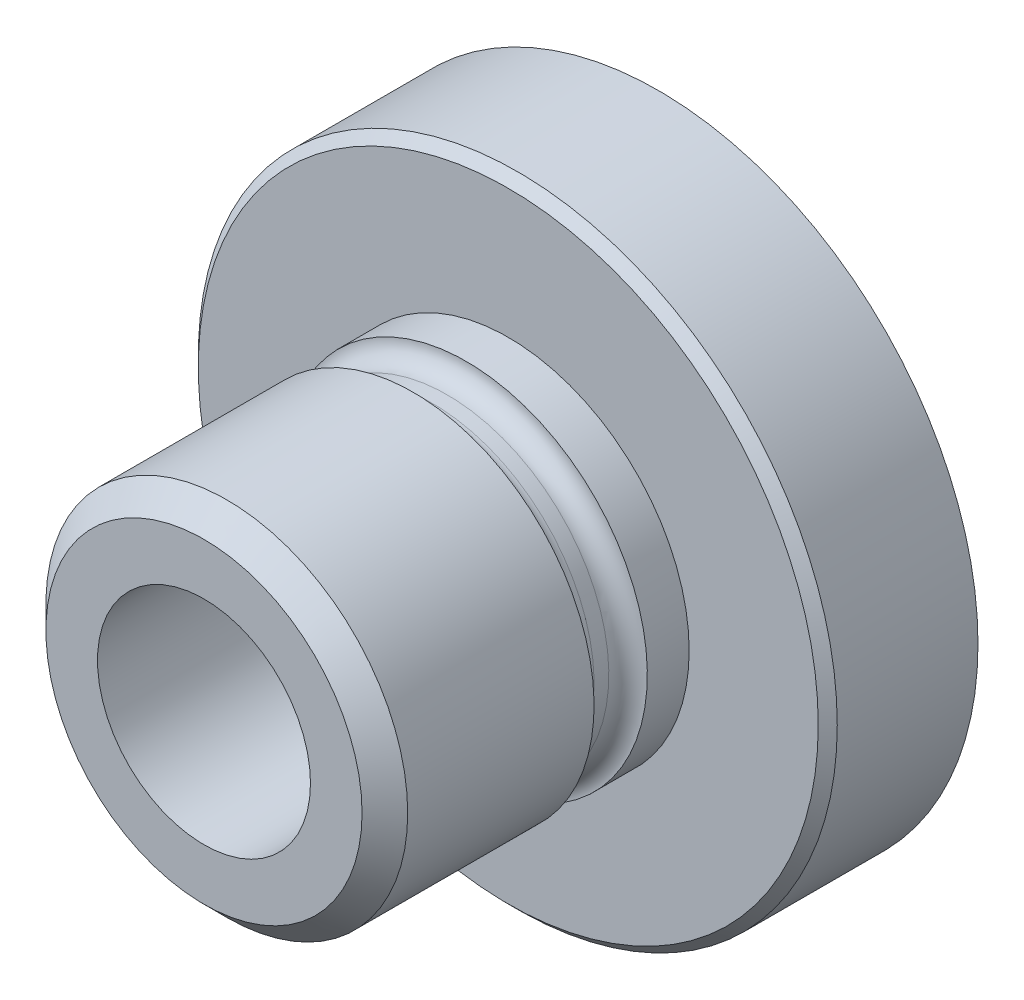
SolidWorks part; units mm, degrees
note: '?' marks a value the reader was unsure of.
ref_plane "Front" through (0, 0, 0) normal (0, 0, 1) x (1, 0, 0)
ref_plane "Top" through (0, 0, 0) normal (0, 1, 0) x (1, 0, 0)
ref_plane "Right" through (0, 0, 0) normal (1, 0, 0) x (0, 0, -1)
sketch "Sketch1" plane through (0, 0, 0) normal (0, 0, 1) x (1, 0, 0)
  circle A0 centre (0, 0) radius 16.8
  dimension "D1" = 33.6
extrude "Extrude1" add sketch "Sketch1" along normal blind 7.9
sketch "Sketch2" plane through (0, 0, 7.9) normal (0, 0, 1) x (1, 0, 0)
  circle A0 centre (0, 0) radius 9.5123
  dimension "D1" = 19.0246
extrude "THREAD" add sketch "Sketch2" along normal blind 16
sketch "Sketch3" plane through (0, 0, 0) normal (1, 0, 0) x (0, 0, -1)
  line L0 (-7.9, 9.5123) -> (-23.9, 9.5123) construction
  line L2 (-11.8877, 8.5) -> (-11.1123, 8.5)
  line L4 (-10.1, 9.5123) -> (-12.9, 9.5123)
  line L5 (-23.9, 9.5123) -> (-23.9, -9.5123) construction
  line L6 (-23.9, 0) -> (0, 0) construction
  arc A0 (-11.8877, 8.5) -> (-12.9, 9.5123) centre (-11.8877, 9.5123) cw
  arc A1 (-10.1, 9.5123) -> (-11.1123, 8.5) centre (-11.1123, 9.5123) cw
  dimension "D1" = 13.8
  dimension "D2" = 2.8
  dimension "D3" = 17
revolve "THREAD END" cut sketch "Sketch3" angle 360 about L6
chamfer "Chamfer1" distance 1.2 angle 45 1 edges at (9.5123, 0, 23.9)
chamfer "Chamfer2" distance 0.5 angle 45 1 edges at (16.8, 0, 7.9)
ref_plane "Plane1" through (0, 16.8, 0) normal (0, 1, 0) x (-1, 0, 0)
hole_wizard "1/8 NPT Tapped Hole1" [suppressed] positions "Sketch5" profile "Sketch4" size "1/8" standard "Ansi Inch"
sketch "Sketch5" plane through (0, 11, 0) normal (0, 1, 0) x (-1, 0, 0)
  line L0 (-11, 0) -> (11, 0) construction
  point P1 (0, 6.3)
  dimension "D1" = 9.5
sketch "Sketch4" plane through (0, 11, 6.3) normal (1, 0, 0) x (0, 0, 1)
  line L0 (0, 0) -> (0, 14.2325)
  line L1 (4.2164, 11.699) -> (0, 14.2325)
  line L2 (-4.2164, 11.699) -> (0, 14.2325) construction
  line L3 (4.2164, 11.699) -> (4.2164, 7)
  line L4 (4.2164, 7) -> (4.9362, 7)
  line L5 (4.9362, 7) -> (5.1458, 0)
  line L6 (-4.9362, 7) -> (-5.1458, 0) construction
  line L7 (5.1458, 0) -> (0, 0)
  line L8 (0, -6.35) -> (0, 107.95) construction
  line L11 (-4.2164, 7) -> (-4.9362, 7) construction
  dimension "Tap Drill Dia." = 8.4328
  dimension "Tap Drill Depth" = 11.699
  dimension "Thread Dia." = 10.2915
  dimension "Thread Angle" = 3.43
  dimension "Thread Depth" = 7
  dimension "Drill Angle" = 118
ref_axis "Axis1" [suppressed] through (0, 11, 6.3) along (0, -1, 0)?
sketch "Sketch6" [suppressed] plane through (0, 0, 0) normal (1, 0, 0) x (0, 0, -1)
  line L0 (-1.2, 11) -> (-1.2, 10)
  line L1 (-1.2, 10) -> (-0.2, 11)
  line L2 (0, 11) -> (-1.1542, 11) construction
  line L3 (-0.2, 11) -> (-1.2, 11)
  line L4 (0, -11) -> (0, 11) construction
  dimension "D1" = 45
  dimension "D2" = 1.1
  dimension "D3" = 4.4
revolve "Cut-Revolve1" [suppressed] cut sketch "Sketch6" angle 360 about axis through (0, 11, 6.3) along (0, -1, 0)
hole_wizard "1/4 NPT Tapped Hole1" [suppressed] positions "Sketch8" profile "Sketch7" size "1/4" standard "Ansi Inch"
sketch "Sketch8" plane through (0, 10.2, 0) normal (0, 1, 0) x (-1, 0, 0)
  line L0 (0, 0) -> (0, 4.8) construction
  line L1 (-10.2, 0) -> (10.2, 0) construction
  line L2 (-10.2, 4.8) -> (10.2, 4.8) construction
  point P1 (0, 18.2)
  dimension "D1" = 18.2
sketch "Sketch7" plane through (0, 10.2, 18.2) normal (1, 0, 0) x (0, 0, 1)
  line L0 (0, 0) -> (0, 14.3423)
  line L1 (5.5626, 11) -> (0, 14.3423)
  line L2 (-5.5626, 11) -> (0, 14.3423) construction
  line L3 (5.5626, 11) -> (5.5626, 10)
  line L4 (5.5626, 10) -> (6.558, 10)
  line L5 (6.558, 10) -> (6.8574, 0)
  line L6 (-6.558, 10) -> (-6.8574, 0) construction
  line L7 (6.8574, 0) -> (0, 0)
  line L8 (0, -6.35) -> (0, 107.95) construction
  line L11 (-5.5626, 10) -> (-6.558, 10) construction
  dimension "Tap Drill Dia." = 11.1252
  dimension "Tap Drill Depth" = 11
  dimension "Thread Dia." = 13.7148
  dimension "Thread Angle" = 3.43
  dimension "Thread Depth" = 10
  dimension "Drill Angle" = 118
sketch "Sketch9" plane through (0, 0, 23.9) normal (0, 0, 1) x (1, 0, 0)
  circle A0 centre (0, 0) radius 5.6
  dimension "D1" = 11.2
extrude "RodHole" cut sketch "Sketch9" against normal up to next
